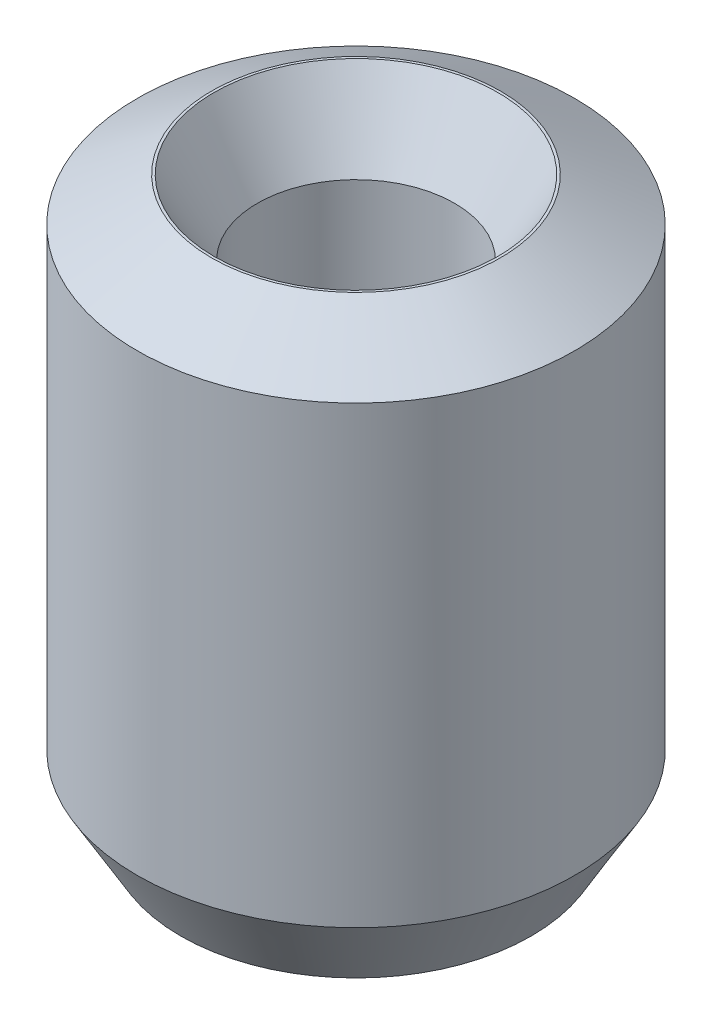
SolidWorks part; units mm, degrees
ref_plane "Front Plane" through (0, 0, 0) normal (0, 0, 1) x (1, 0, 0)
ref_plane "Top Plane" through (0, 0, 0) normal (0, 1, 0) x (1, 0, 0)
ref_plane "Right Plane" through (0, 0, 0) normal (1, 0, 0) x (0, 0, -1)
sketch "Sketch1" plane through (0, 0, 0) normal (0, 1, 0) x (1, 0, 0)
  circle A0 centre (0, 0) radius 20
  dimension "SLEEVE_OD" = 40
extrude "Boss-Extrude1" add sketch "Sketch1" along normal blind 52.305
sketch "Sketch2" plane through (0, 0, 0) normal (0, 1, 0) x (1, 0, 0)
  circle A0 centre (0, 0) radius 9.015
  dimension "BORE_D" = 18.03
extrude "Cut-Extrude1" cut sketch "Sketch2" along normal through all
chamfer "Chamfer1" distance 3.9691 angle 59.673 4 edges at (0, 52.305, 9.015) (0, 0, 9.015) (0, 0, 20) (0, 52.305, 20) first distance on face at (0, 52.305, 9.015) first distance on face at (0, 0, 9.015) first distance on face at (0, 52.305, 20)
